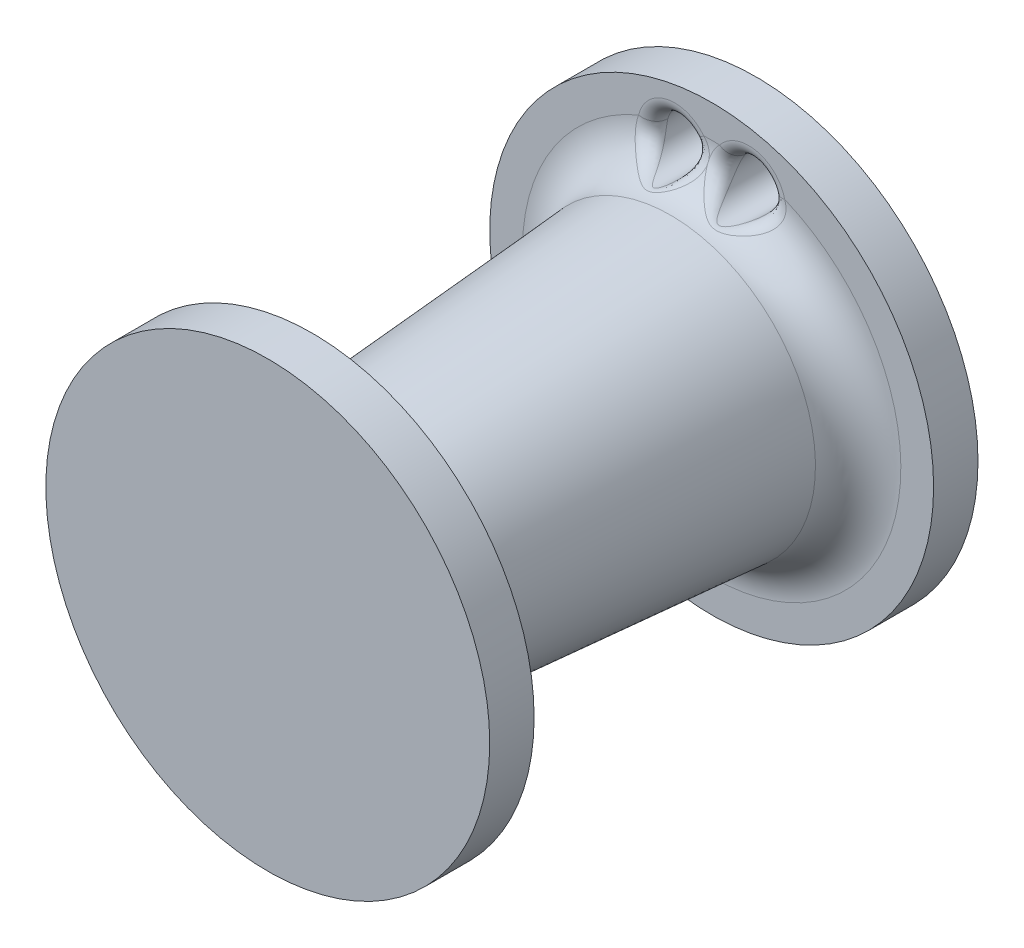
SolidWorks part; units mm, degrees
ref_plane "Plan de face" through (0, 0, 0) normal (0, 0, 1) x (1, 0, 0)
ref_plane "Plan de dessus" through (0, 0, 0) normal (0, 1, 0) x (1, 0, 0)
ref_plane "Plan de droite" through (0, 0, 0) normal (1, 0, 0) x (0, 0, -1)
sketch "Esquisse1" plane through (0, 0, 0) normal (0, 0, 1) x (1, 0, 0)
  circle A0 centre (0, 0) radius 15
  dimension "D1" = 30
extrude "Boss.-Extru.1" add sketch "Esquisse1" along normal blind 35
sketch "Esquisse2" plane through (0, 0, 0) normal (0, 0, -1) x (-1, 0, 0)
  line L1 (-2.0976, -1.7) -> (2.0976, -1.7)
  line L2 (-2.0976, -1.7) -> (-2.0976, 1.7) construction
  line L3 (-2.0976, 1.7) -> (2.0976, 1.7)
  line L4 (2.0976, -1.7) -> (2.0976, 1.7) construction
  line L5 (-2.0976, -1.7) -> (2.0976, 1.7) construction
  line L6 (-2.0976, 1.7) -> (2.0976, -1.7) construction
  circle A0 centre (0, 0) radius 2.7 construction
  arc A1 (-2.0976, 1.7) -> (-2.0976, -1.7) centre (0, 0) ccw
  arc A2 (2.0976, 1.7) -> (2.0976, -1.7) centre (0, 0) cw
  dimension "D1" = 5.4
  dimension "D2" = 3.4
extrude "Enlèv. mat.-Extru.1" cut sketch "Esquisse2" against normal blind 8
sketch "Esquisse3" plane through (0, 0, 0) normal (0, 0, -1) x (-1, 0, 0)
  circle A0 centre (0, 0) radius 4
  dimension "D1" = 8
extrude "Enlèv. mat.-Extru.2" cut sketch "Esquisse3" against normal blind 1
ref_axis "Axe1" through (0, 0, 1) along (0, 0, -1)
sketch "Esquisse4" plane through (0, 0, 0) normal (1, 0, 0) x (0, 0, -1)
  line L0 (0, 15) -> (-35, 15) construction
  line L1 (-31, 15) -> (-4, 15)
  line L2 (-31, 15) -> (-31, 10)
  line L3 (-31, 10) -> (-4, 10) construction
  line L4 (-4, 15) -> (-4, 10)
  line L5 (0, 10) -> (-4, 10) construction
  line L6 (0, -15) -> (0, 15) construction
  line L7 (-31, 10) -> (-35, 10) construction
  line L8 (-35, 15) -> (-35, -15) construction
  line L9 (-31, 10) -> (-31, 8)
  line L10 (-31, 8) -> (-4, 10)
  dimension "D1" = 10
  dimension "D2" = 4
  dimension "D3" = 8
revolve "Enlèvement de matière-Révolution1" cut sketch "Esquisse4" angle 360 about axis through (0, 0, 1) along (0, 0, -1)
fillet "Congé2" radius 3 2 edges at (10, 0, 4) (8, 0, 31)
sketch "Esquisse5" plane through (0, 0, 0) normal (0, 0, -1) x (-1, 0, 0)
  line L0 (2.5, 11.225) -> (-2.5, 11.225) construction
  circle A0 centre (0, 0) radius 11.5 construction
  circle A1 centre (-2.5, 11.225) radius 1.5
  circle A2 centre (2.5, 11.225) radius 1.5
  dimension "D1" = 23
  dimension "D3" = 3
  dimension "D2" = 5
extrude "Enlèv. mat.-Extru.3" cut sketch "Esquisse5" against normal up to next
fillet "Congé3" radius 1 4 edges at (-2.8261, 12.6891, 4) (2.8261, 12.6891, 4) (-2.4305, 12.7234, 4.0047) (3.1209, 12.5904, 4.0057)
sketch "Esquisse6" plane through (0, 0, 0) normal (1, 0, 0) x (0, 0, -1)
  line L0 (-31, 15) -> (-35, 15) construction
  line L1 (0, 15) -> (-1, 15)
  line L2 (0, 15) -> (0, 7)
  line L3 (0, 7) -> (-1, 7)
  line L4 (-1, 15) -> (-1, 7)
  line L5 (-35, 15) -> (-34, 15)
  line L6 (-35, 15) -> (-35, 0)
  line L7 (-35, 0) -> (-34, 0)
  line L8 (-34, 15) -> (-34, 0)
  line L9 (-35, 15) -> (-35, -15) construction
  dimension "D1" = 1
  dimension "D2" = 8
  dimension "D3" = 1
revolve "Enlèvement de matière-Révolution2" cut sketch "Esquisse6" angle 360 about axis through (0, 0, 1) along (0, 0, -1)
